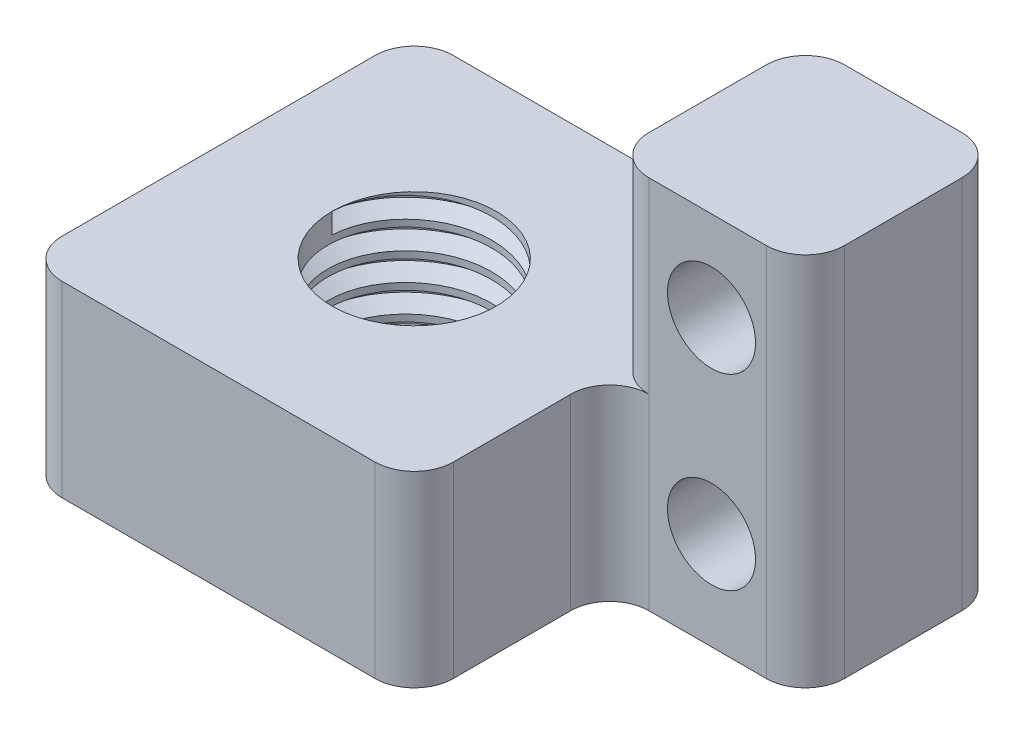
SolidWorks part; units mm, degrees
ref_plane "Front Plane" through (0, 0, 0) normal (0, 0, 1) x (1, 0, 0)
ref_plane "Top Plane" through (0, 0, 0) normal (0, 1, 0) x (1, 0, 0)
ref_plane "Right Plane" through (0, 0, 0) normal (1, 0, 0) x (0, 0, -1)
sketch "Sketch1" plane through (0, 0, 0) normal (0, 1, 0) x (1, 0, 0)
  line L1 (-5, -5) -> (5, -5)
  line L2 (-5, -5) -> (-5, 5)
  line L3 (-5, 5) -> (5, 5)
  line L4 (5, -5) -> (5, 5)
  line L5 (-5, -5) -> (5, 5) construction
  line L6 (-5, 5) -> (5, -5) construction
  line L7 (5, 5) -> (10, 5)
  line L8 (5, 5) -> (5, 0)
  line L9 (5, 0) -> (10, 0)
  line L10 (10, 5) -> (10, 0)
  circle A0 centre (0, 0) radius 2.1
  dimension "D1" = 4.2
  dimension "D2" = 10
  dimension "D3" = 5
  dimension "D4" = 5
extrude "Boss-Extrude1" add sketch "Sketch1" along normal blind 4.7929 contours L10 L7 L4 L9 | L1 L4 L3 L2 A0 region at (-4.8586, 0, 0) region at (7.5, 0, -2.5)
extrude "Boss-Extrude2" add sketch "Sketch1<3>" along normal blind 9.5858 contours L10 L7 L4 L9 region at (7.5, 0, -2.5)
sketch "Sketch1<3>" plane through (0, 0, 0) normal (0, 1, 0) x (1, 0, 0) same geometry as "Sketch1"
thread "Thread1" pitch 0.7 method cut profile "Thread Profile1" start angle 0, offset 0, length 5.2929, pitch 0.7, diameter 4.2
ref_plane "Plane1" through (-2.1, 4.7929, 0) normal (0, 0, 1) x (-1, 0, 0)
sketch "Thread Profile1" plane through (-2.1, 4.7929, 0) normal (0, 0, 1) x (-1, 0, 0)
  line L0 (0, 0) -> (0, 0.7) construction
  line L1 (0, 0) -> (0.3789, 0.2187)
  line L2 (0.3789, 0.2187) -> (0.3789, 0.3062)
  line L3 (0.3789, 0.3062) -> (0, 0.525)
  line L4 (0.3789, 0.2625) -> (0, 0.2625) construction
  line L11 (0, 0) -> (0, 0.525)
  point P2 (0, 0)
  dimension "Pitch" = 0.7
  dimension "Profile_Angle" = 60
  dimension "Profile_Land" = 0.0875
  dimension "Profile_Height" = 0.3789
sketch "Sketch5" plane through (0, 0, 0) normal (0, 0, 1) x (1, 0, 0)
  line L0 (5, 0) -> (10, 0) construction
  line L2 (10, 9.5858) -> (10, 0) construction
  line L3 (7.6, 7.29) -> (7.6, 2.5) construction
  circle A1 centre (7.6, 2.5) radius 1.125
  circle A2 centre (7.6, 7.29) radius 1.125
  dimension "D1" = 2.25
  dimension "D3" = 2.25
  dimension "D2" = 2.5
  dimension "D4" = 2.4
  dimension "D5" = 4.79
extrude "Cut-Extrude1" cut sketch "Sketch5" against normal through all
fillet "Fillet2" radius 1 7 edges at (5, 7.1893, -5) (-5, 2.3964, -5) (5, 2.3964, 0) (10, 4.7929, 0) (10, 4.7929, -5) (5, 2.3964, 5) (-5, 2.3964, 5)
fillet "Fillet3" radius 1 1 edges at (5, 7.1893, 0)
